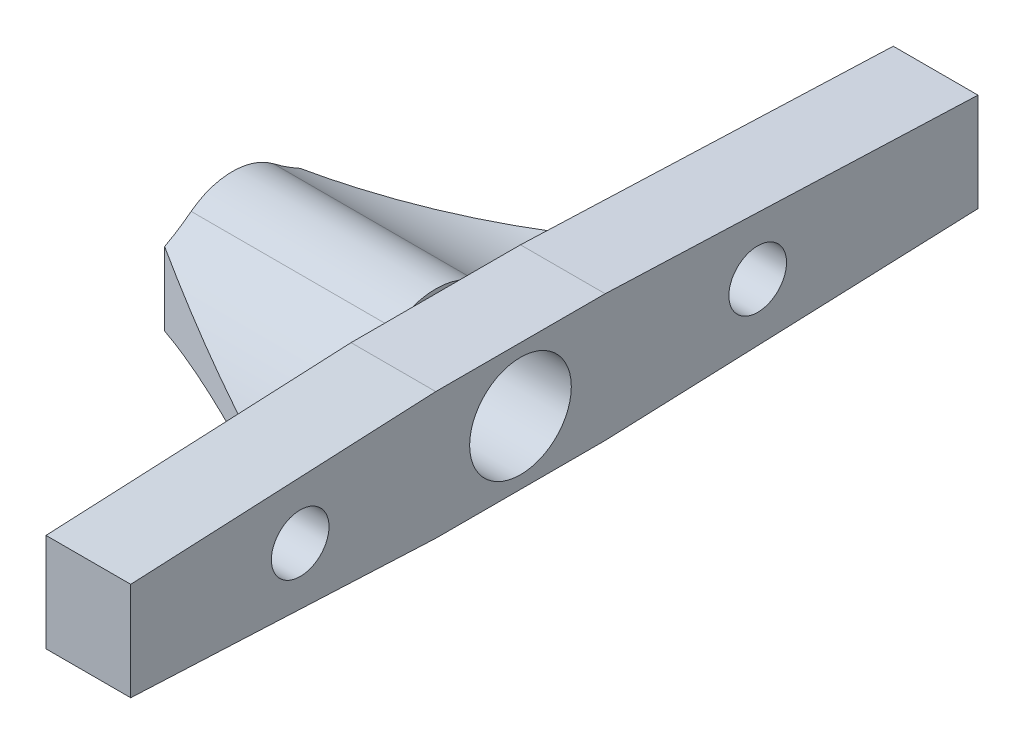
SolidWorks part; units mm, degrees
ref_plane "Front Plane" through (0, 0, 0) normal (0, 0, 1) x (1, 0, 0)
ref_plane "Top Plane" through (0, 0, 0) normal (0, 1, 0) x (1, 0, 0)
ref_plane "Right Plane" through (0, 0, 0) normal (1, 0, 0) x (0, 0, -1)
sketch "Sketch1" plane through (0, 0, 0) normal (1, 0, 0) x (0, 0, -1)
  line L1 (27, -3.75) -> (-23, -3.75)
  line L2 (27, -3.75) -> (27, 3.75)
  line L3 (27, 3.75) -> (-23, 3.75)
  line L4 (-23, -3.75) -> (-23, 3.75)
  line L5 (27, -3.75) -> (-23, 3.75) construction
  line L6 (27, 3.75) -> (-23, -3.75) construction
  circle A0 centre (0, 0) radius 3
  point P3 (2, 0)
  dimension "D1" = 6
  dimension "D2" = 7.5
  dimension "D3" = 50
  dimension "D4" = 2
extrude "Boss-Extrude1" add sketch "Sketch1" along normal blind 5
sketch "Sketch2" plane through (0, 0, 0) normal (-1, 0, 0) x (0, 0, 1)
  circle A0 centre (0, 0) radius 4
  circle A1 centre (0, 0) radius 3
  dimension "D1" = 8
extrude "Boss-Extrude2" add sketch "Sketch2" along normal blind 12
sketch "Sketch3" plane through (0, 0, 0) normal (0, 1, 0) x (1, 0, 0)
  line L1 (-12, 4) -> (-12, -4) construction
  line L2 (0, -4.125) -> (0, 4.125) construction
  line L4 (-12, 4) -> (0, 11.4)
  line L5 (0, 11.4) -> (0, 3.4)
  line L6 (0, 3.4) -> (-12, 3.4)
  line L7 (-12, 3.4) -> (-12, 4)
  line L12 (-12, -3.4) -> (0, -3.4)
  line L13 (0, -3.4) -> (0, -10.4)
  line L14 (0, -10.4) -> (-12, -4)
  line L15 (-12, -4) -> (-12, -3.4)
  dimension "D1" = 0.6
  dimension "D2" = 8
  dimension "D3" = 0.6
  dimension "D4" = 7
extrude "Boss-Extrude3" add sketch "Sketch3" along normal blind 0.7 and the other way blind 0.7
chamfer "Chamfer1" [suppressed] distance 18 angle 4
chamfer "Chamfer2" [suppressed] distance 22 angle 4
chamfer "Chamfer3" [suppressed] distance 18 angle 4
chamfer "Chamfer4" [suppressed] distance 22 angle 4
sketch "Sketch4" plane through (0, 0, 0) normal (-1, 0, 0) x (0, 0, 1)
  line L0 (9.35, 0) -> (-9.35, 0) construction
  line L1 (-12.5566, 2.5) -> (-15.4434, 2.5)
  line L2 (-15.4434, 2.5) -> (-16.8868, 0)
  line L3 (-16.8868, 0) -> (-15.4434, -2.5)
  line L4 (-15.4434, -2.5) -> (-12.5566, -2.5)
  line L5 (-12.5566, -2.5) -> (-11.1132, 0)
  line L6 (-11.1132, 0) -> (-12.5566, 2.5)
  line L7 (0, -4.4) -> (0, 4.4) construction
  line L8 (14.4434, 2.5) -> (11.5566, 2.5)
  line L9 (11.5566, 2.5) -> (10.1132, 0)
  line L10 (10.1132, 0) -> (11.5566, -2.5)
  line L11 (11.5566, -2.5) -> (14.4434, -2.5)
  line L12 (14.4434, -2.5) -> (15.8868, 0)
  line L13 (15.8868, 0) -> (14.4434, 2.5)
  circle A0 centre (-14, 0) radius 2.5 construction
  circle A1 centre (13, 0) radius 2.5 construction
  dimension "D1" = 5
  dimension "D2" = 14
  dimension "D3" = 13
extrude "Cut-Extrude1" cut sketch "Sketch4" against normal blind 2
hole_wizard "M3 Clearance Hole1" positions "Sketch6" profile "Sketch7" hole size "M3" standard "ANSI Metric"
sketch "Sketch6" plane through (2, 0, 0) normal (-1, 0, 0) x (0, 0, 1)
  line L0 (9.35, 0) -> (-9.35, 0) construction
  point P0 (-14, 0)
  point P4 (13, 0)
sketch "Sketch7" plane through (2, 0, -14) normal (0, 1, 0) x (0, 0, 1)
  line L0 (0, 0) -> (0, 13.0215)
  line L1 (0, 13.0215) -> (1.7, 12)
  line L2 (1.7, 12) -> (1.7, 0)
  line L5 (1.7, 0) -> (0, 0)
  line L10 (0, 13.0215) -> (-1.7, 12) construction
  line L11 (0, -6.35) -> (0, 107.95) construction
  dimension "Hole Dia." = 3.4
  dimension "Hole Depth" = 12
  dimension "Drill Angle" = 118
fillet "Fillet1" radius 12 4 edges at (-6, -0.7, 3.9383) (-6, -0.7, -3.9383) (-6, 0.7, -3.9383) (-6, 0.7, 3.9383)
sketch "Sketch10" plane through (5, 0, 0) normal (1, 0, 0) x (0, 0, -1)
  line L0 (-23, 2.9) -> (-5, 3.75)
  line L1 (-23, 3.75) -> (-23, -3.75) construction
  line L2 (27, 3.75) -> (-23, 3.75) construction
  line L3 (-5, 3.75) -> (-0.4811, 5.0493)
  line L4 (-0.4811, 5.0493) -> (5, 3.75)
  line L5 (5, 3.75) -> (27, 2.9)
  line L6 (27, -3.75) -> (27, 3.75) construction
  line L7 (-23, 2.9) -> (-23, -2.9)
  line L8 (27, 2.9) -> (27, -2.9)
  line L9 (9.35, 0) -> (-9.35, 0) construction
  line L10 (5, -3.75) -> (27, -2.9)
  line L11 (-0.4811, -5.0493) -> (5, -3.75)
  line L12 (-5, -3.75) -> (-0.4811, -5.0493)
  line L13 (-23, -2.9) -> (-5, -3.75)
  line L15 (-28.1007, 8.3187) -> (30.426, 8.3187)
  line L16 (-28.1007, 8.3187) -> (-28.1007, -8.958)
  line L17 (-28.1007, -8.958) -> (30.426, -8.958)
  line L18 (30.426, 8.3187) -> (30.426, -8.958)
  point P12 (27, 0)
  point P20 (-23, 0)
  dimension "D1" = 18
  dimension "D2" = 22
  dimension "D3" = 5.8
  dimension "D4" = 5.8
extrude "Cut-Extrude2" cut sketch "Sketch10" against normal blind 10
sketch "Sketch11" plane through (5, 0, 0) normal (1, 0, 0) x (0, 0, -1)
  line L1 (-24.609, 4.8639) -> (-20, 4.8639)
  line L2 (-24.609, 4.8639) -> (-24.609, -5.1401)
  line L3 (-24.609, -5.1401) -> (-20, -5.1401)
  line L4 (-20, 4.8639) -> (-20, -5.1401)
  line L5 (20, 4.6495) -> (33.0514, 4.6495)
  line L6 (20, 4.6495) -> (20, -7.248)
  line L7 (20, -7.248) -> (33.0514, -7.248)
  line L8 (33.0514, 4.6495) -> (33.0514, -7.248)
  dimension "D1" = 20
  dimension "D2" = 20
extrude "Cut-Extrude3" [suppressed] cut sketch "Sketch11" against normal blind 10
equation "\"D2@Boss-Extrude3\"=\"D1@Boss-Extrude3\""
